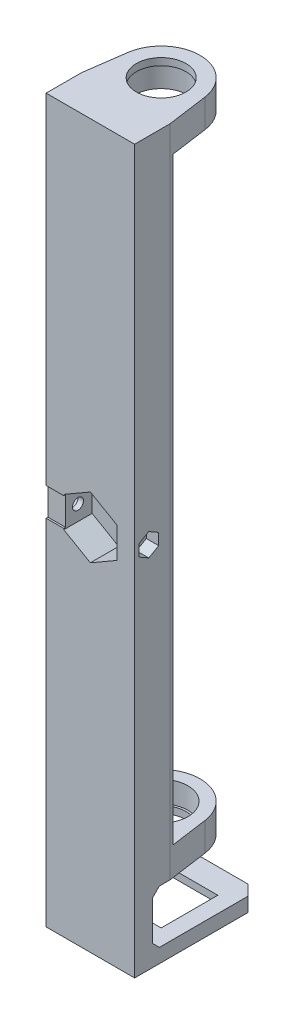
SolidWorks part; units mm, degrees
other "Markup1"
sketch "Sketch20" plane through (12.5, 200, 20) normal (0, 0.0878, 0.9961) x (0.9932, -0.1157, 0.0102)
ref_plane "Front Plane" through (0, 0, 0) normal (0, 0, 1) x (1, 0, 0)
ref_plane "Top Plane" through (0, 0, 0) normal (0, 1, 0) x (1, 0, 0)
ref_plane "Right Plane" through (0, 0, 0) normal (1, 0, 0) x (0, 0, -1)
sketch "Sketch1" plane through (0, 0, 0) normal (0, 1, 0) x (1, 0, 0)
  line L0 (0, 13.844) -> (0, -25.2925) construction
  line L1 (-12.5, -10) -> (-10.8947, 1.5184)
  line L2 (-12.5, -10) -> (-12.5, -20)
  line L3 (-12.5, -20) -> (12.5, -20)
  line L4 (12.5, -10) -> (12.5, -20)
  line L5 (12.5, -10) -> (10.8947, 1.5184)
  arc A0 (10.8947, 1.5184) -> (-10.8947, 1.5184) centre (0, 0) ccw
  point P10 (0, -20)
  dimension "D1" = 22
  dimension "D2" = 25
  dimension "D3" = 10
  dimension "D4" = 10
extrude "Boss-Extrude1" add sketch "Sketch1" along normal blind 200
sketch "Sketch4" plane through (0, 0, 0) normal (0, -1, 0) x (1, 0, 0)
  circle A0 centre (0, 0) radius 7
  dimension "D1" = 14
extrude "Cut-Extrude2" cut sketch "Sketch4" against normal blind 200
sketch "Sketch3" plane through (0, 0, 0) normal (1, 0, 0) x (0, 0, -1)
  line L0 (11, 0) -> (11, 200) construction
  line L1 (11, 192) -> (-9, 192)
  line L2 (11, 192) -> (11, 23)
  line L3 (11, 23) -> (-9, 23)
  line L4 (-9, 192) -> (-9, 23)
  line L5 (11, 200) -> (1.5184, 200) construction
  line L7 (-10, 200) -> (-10, 0) construction
  line L8 (11, 0) -> (-10, 0)
  line L9 (11, 0) -> (11, 15)
  line L10 (11, 15) -> (-10, 15)
  line L11 (-10, 0) -> (-10, 15)
  dimension "D1" = 20
  dimension "D2" = 8
  dimension "D3" = 15
  dimension "D4" = 8
extrude "Cut-Extrude1" cut sketch "Sketch3" against normal mid plane 200
sketch "Sketch5" plane through (0, 192, 0) normal (0, -1, 0) x (1, 0, 0)
  circle A0 centre (0, 0) radius 7.565
  dimension "D1" = 15.13
extrude "Cut-Extrude3" cut sketch "Sketch5" against normal blind 6
sketch "Sketch6" plane through (0, 23, 0) normal (0, 1, 0) x (1, 0, 0)
  circle A0 centre (0, 0) radius 7.565
  dimension "D1" = 15.13
extrude "Cut-Extrude4" cut sketch "Sketch6" against normal blind 6
sketch "Sketch7" plane through (0, 0, 20) normal (0, 0, 1) x (1, 0, 0)
  line L0 (0, 200) -> (0, 0) construction
  line L1 (-12.5, 200) -> (12.5, 200) construction
  line L2 (-12.5, 100) -> (12.5, 100) construction
  line L3 (-12.5, 200) -> (-12.5, 0) construction
  line L4 (12.5, 200) -> (12.5, 0) construction
  circle A0 centre (0, 100) radius 4.85
  dimension "D1" = 9.7
extrude "Boss-Extrude2" [suppressed] add sketch "Sketch7" along normal blind 29 from surface starting at face at (0, 100, 20)
sketch "Sketch9" [suppressed] plane through (0, 0, 49) normal (0, 0, 1) x (1, 0, 0)
  circle A0 centre (0, 100) radius 2.05
  dimension "D1" = 4.1
sketch "Sketch11" plane through (0, 0, 0) normal (0, -1, 0) x (1, 0, 0)
  line L1 (0, -1000) -> (0, 49000) construction
  line L3 (-5.5, 21.5) -> (-5.5, 19.5)
  line L5 (-12.5, 20) -> (12.5, 20) construction
  line L6 (12.5, 21.5) -> (5.5, 21.5) construction
  line L7 (12.5, 21.5) -> (12.5, 19.5) construction
  line L8 (12.5, 19.5) -> (5.5, 19.5) construction
  line L9 (5.5, 21.5) -> (5.5, 19.5) construction
  line L10 (12.5, 20) -> (12.5, 10) construction
  line L11 (-12.5, 19.5) -> (-5.5, 19.5)
  line L12 (-12.5, 21.5) -> (-12.5, 19.5)
  line L13 (-12.5, 21.5) -> (-5.5, 21.5)
  dimension "D1" = 0.5
  dimension "D2" = 2
  dimension "D3" = 7
extrude "Cut-Extrude8" cut sketch "Sketch11" against normal mid plane 8 from offset 100 offset against normal yes
extrude "Cut-Extrude9" [suppressed] cut sketch "Sketch9" against normal blind 4
sketch "Sketch12" plane through (0, 0, 0) normal (0, 0, 1) x (1, 0, 0)
  line L0 (0, 104.75) -> (0, 95.25) construction
  line L1 (-4.75, 100) -> (4.75, 100) construction
  line L2 (1.3973, 101.5) -> (-1.3973, 101.5)
  line L3 (-2.6401, 97.95) -> (3.2254, 97.95) construction
  arc A2 (-1.3973, 101.5) -> (1.3973, 101.5) centre (0, 100) ccw
  dimension "D1" = 4.1
  dimension "D2" = 3.55
extrude "Cut-Extrude10" [suppressed] cut sketch "Sketch12" against normal through all both and the other way through all from surface starting at face at (-4.5, 100, 20)
fillet "Fillet1" [suppressed] radius 2
sketch "Sketch13" plane through (0, 0, 0) normal (0, -1, 0) x (1, 0, 0)
  line L0 (12.5, 20) -> (12.5, 10) construction
  line L1 (-12.5, 20) -> (12.5, 20)
  line L2 (-12.5, 20) -> (-12.5, -12)
  line L3 (-9.5, -15) -> (9.5, -15)
  line L4 (12.5, 20) -> (12.5, -12)
  line L5 (-12.5, -12) -> (-9.5, -15)
  line L6 (-8, 8) -> (8, 8)
  line L7 (-8, 8) -> (-8, -8)
  line L8 (-8, -8) -> (8, -8)
  line L9 (8, 8) -> (8, -8)
  line L10 (9.5, -15) -> (12.5, -12)
  line L12 (-8.5, 8.5) -> (8.5, 8.5) construction
  line L13 (-8.5, 8.5) -> (-8.5, -8.5) construction
  line L14 (-8.5, -8.5) -> (8.5, -8.5) construction
  line L15 (8.5, 8.5) -> (8.5, -8.5) construction
  point P1 (12.5, -15)
  point P2 (-12.5, -15)
  point P11 (0, 8)
  point P13 (8, 0)
  point P22 (0, 8.5)
  point P23 (8.5, 0)
  dimension "D1" = 35
  dimension "D2" = 16
  dimension "D4" = 17
  dimension "D5" = 17
extrude "Boss-Extrude3" add sketch "Sketch13" along normal blind 4
sketch "Sketch14" plane through (-12.5, 0, 0) normal (-1, 0, 0) x (0, 0, 1)
  line L1 (15, 15) -> (10, 15)
  line L2 (15, 15) -> (15, 0)
  line L3 (15, 0) -> (10, 0)
  line L4 (10, 15) -> (10, 0)
  dimension "D1" = 5
extrude "Cut-Extrude11" cut sketch "Sketch14" against normal through all
chamfer "Chamfer1" distance 2 angle 45 2 edges at (0, 15, 15) (0, 0, 15)
sketch "Sketch15" plane through (0, -4, 0) normal (0, -1, 0) x (1, 0, 0)
  line L1 (-11.5, 11.5) -> (11.5, 11.5)
  line L2 (-11.5, 11.5) -> (-11.5, -11.5)
  line L3 (-11.5, -11.5) -> (11.5, -11.5)
  line L4 (11.5, 11.5) -> (11.5, -11.5)
  point P4 (-11.5, 0)
  point P6 (0, -11.5)
  dimension "D1" = 23
  dimension "D2" = 23
extrude "Cut-Extrude12" cut sketch "Sketch15" against normal blind 2
sketch "Sketch16" plane through (0, 0, 20) normal (0, 0, 1) x (1, 0, 0)
  line L0 (12.5, 200) -> (12.5, -4) construction
  line L1 (0, 108.6603) -> (-7.5, 104.3301)
  line L2 (-7.5, 104.3301) -> (-7.5, 95.6699)
  line L3 (-7.5, 95.6699) -> (0, 91.3397)
  line L4 (0, 91.3397) -> (7.5, 95.6699)
  line L5 (7.5, 95.6699) -> (7.5, 104.3301)
  line L6 (7.5, 104.3301) -> (0, 108.6603)
  line L7 (-12.5, 200) -> (-12.5, 104) construction
  line L8 (12.5, -4) -> (-12.5, -4) construction
  circle A0 centre (0, 100) radius 7.5 construction
  point P15 (0.1274, 99.2949)
  dimension "D1" = 15
  dimension "D2" = 12.5
  dimension "D3" = 104
extrude "Cut-Extrude13" cut sketch "Sketch16" against normal blind 8
sketch "Sketch17" plane through (-12.5, 0, 0) normal (-1, 0, 0) x (0, 0, 1)
  line L0 (20, -4) -> (-12, -4) construction
  line L1 (20, 200) -> (20, 104) construction
  circle A0 centre (16, 100) radius 1.55
  dimension "D2" = 3.1
  dimension "D1" = 104
  dimension "D3" = 4
extrude "Cut-Extrude14" cut sketch "Sketch17" against normal through all
sketch "Sketch18" plane through (-12.5, 0, 0) normal (-1, 0, 0) x (0, 0, 1)
  circle A0 centre (16, 100) radius 2.75
  circle A1 centre (16, 100) radius 1.55 construction
  dimension "D1" = 5.5
extrude "Cut-Extrude15" cut sketch "Sketch18" against normal blind 3.5
sketch "Sketch19" plane through (12.5, 0, 0) normal (1, 0, 0) x (0, 0, -1)
  line L0 (-9, 23) -> (-9, 192) construction
  line L1 (-16, 103.2332) -> (-18.8, 101.6166)
  line L2 (-18.8, 101.6166) -> (-18.8, 98.3834)
  line L3 (-18.8, 98.3834) -> (-16, 96.7668)
  line L4 (-16, 96.7668) -> (-13.2, 98.3834)
  line L5 (-13.2, 98.3834) -> (-13.2, 101.6166)
  line L6 (-13.2, 101.6166) -> (-16, 103.2332)
  circle A0 centre (-16, 100) radius 2.8 construction
  dimension "D1" = 5.6
extrude "Cut-Extrude16" cut sketch "Sketch19" against normal blind 3.5
fillet "Fillet2" radius 1 1 edges at (-12.5, 100, 18.75)
